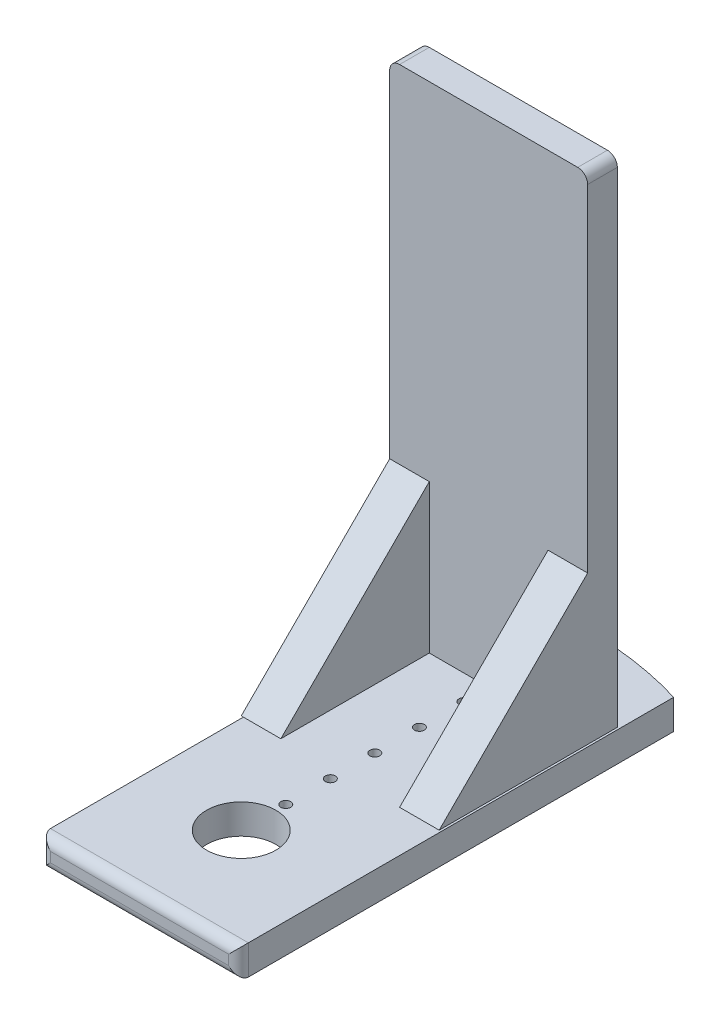
SolidWorks part; units mm, degrees
ref_plane "前视基准面" through (0, 0, 0) normal (0, 0, 1) x (1, 0, 0)
ref_plane "上视基准面" through (0, 0, 0) normal (0, 1, 0) x (1, 0, 0)
ref_plane "右视基准面" through (0, 0, 0) normal (1, 0, 0) x (0, 0, -1)
sketch "草图1" plane through (0, 0, 0) normal (0, 1, 0) x (1, 0, 0)
  line L0 (0, 0) -> (0, 35) construction
  line L1 (0, 4.5) -> (0, 39.5) construction
  line L2 (0, 9) -> (0, 44) construction
  line L3 (0, 13.5) -> (0, 48.5) construction
  line L4 (0, 18) -> (0, 53) construction
  line L5 (0, 22.5) -> (0, 57.5) construction
  line L6 (10.2163, 33.4758) -> (10.2163, -10.4949)
  line L7 (10.2163, -10.4949) -> (-9.7837, -10.4949)
  line L8 (-9.7837, -10.4949) -> (-9.7837, 33.6048)
  line L9 (0, 0) -> (0.5, -24.2583) construction
  arc A0 (10.2163, 33.4758) -> (-9.7837, 33.6048) centre (0, 0) ccw
  circle A1 centre (0, 0) radius 3.5
  circle A3 centre (0, 0) radius 0.5 construction
  circle A9 centre (0, 4.5) radius 0.5
  circle A10 centre (0, 9) radius 0.5
  circle A11 centre (0, 13.5) radius 0.5
  circle A12 centre (0, 18) radius 0.5
  circle A13 centre (0, 22.5) radius 0.5
  point P31 (0.2163, -10.4949)
  dimension "D1" = 7
  dimension "D2" = 70
  dimension "D3" = 1
  dimension "D5" = 20
  dimension "D4" = 6
extrude "凸台-拉伸1" add sketch "草图1" along normal blind 3
sketch "草图3" plane through (0, 3, 0) normal (0, 1, 0) x (1, 0, 0)
  line L0 (0, 0) -> (0, 35) construction
  line L2 (10, 28) -> (-10, 28)
  line L3 (10, 28) -> (10, 25)
  line L4 (10, 25) -> (-10, 25)
  line L5 (-10, 28) -> (-10, 25)
  circle A0 centre (0, 0) radius 35 construction
  point P10 (0, 25)
  dimension "D1" = 3
  dimension "D2" = 20
  dimension "D3" = 25
extrude "凸台-拉伸2" add sketch "草图3" along normal blind 50
sketch "草图5" plane through (-10, 0, 0) normal (-1, 0, 0) x (0, 0, 1)
  line L0 (-25, 18) -> (-10, 3)
  line L1 (-25, 53) -> (-25, 3) construction
  line L2 (-25, 18) -> (-25, 3)
  line L3 (-25, 3) -> (-10, 3)
  dimension "D1" = 15
  dimension "D2" = 15
extrude "凸台-拉伸3" add sketch "草图5" against normal blind 4
sketch "草图6" plane through (10, 0, -10) normal (-1, 0, 0) x (0, 0, 1)
  line L0 (-15, 18) -> (0, 3)
  line L2 (-15, 18) -> (-15, 3)
  line L3 (-15, 3) -> (0, 3)
  line L4 (-15, 53) -> (-15, 3) construction
  point P2 (-15, 3)
  dimension "D1" = 15
  dimension "D2" = 15
extrude "凸台-拉伸4" add sketch "草图6" along normal blind 4
fillet "圆角2" radius 1 4 edges at (-9.7837, 1.5, 10.4949) (0.2163, 3, 10.4949) (10.2163, 1.5, 10.4949) (0.2163, 0, 10.4949)
fillet "圆角3" radius 1 2 edges at (10, 53, -26.5) (-10, 53, -26.5)
